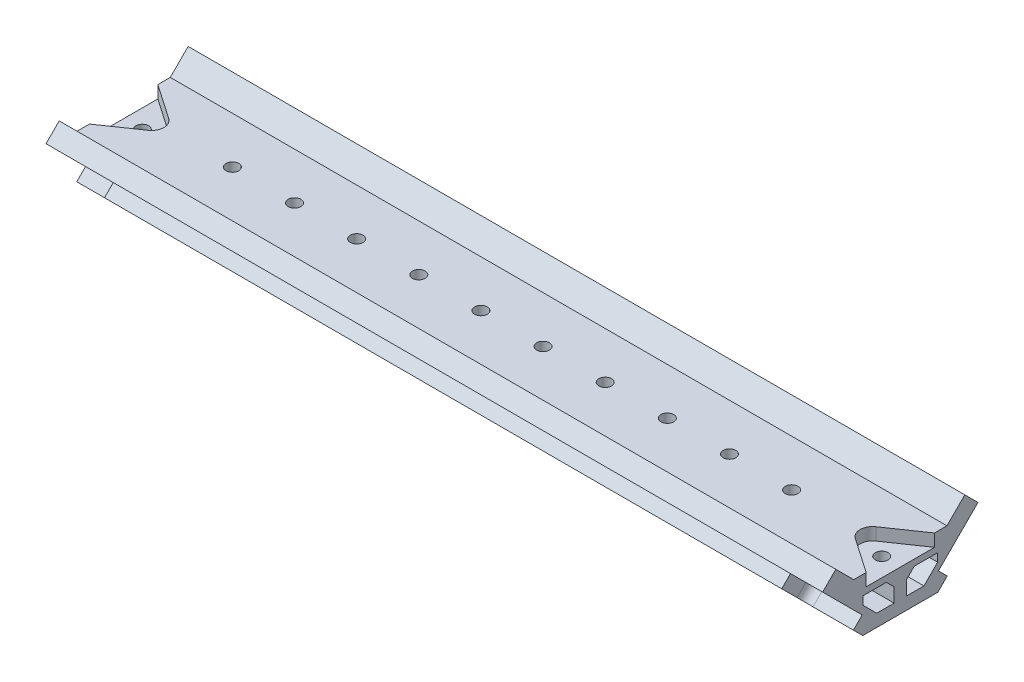
SolidWorks part; units mm, degrees
ref_plane "Front Plane" through (0, 0, 0) normal (0, 0, 1) x (1, 0, 0)
ref_plane "Top Plane" through (0, 0, 0) normal (0, 1, 0) x (1, 0, 0)
ref_plane "Right Plane" through (0, 0, 0) normal (1, 0, 0) x (0, 0, -1)
sketch "Sketch1" plane through (0, 0, 0) normal (1, 0, 0) x (0, 0, -1)
  line L1 (-25, 0) -> (25, 0)
  line L2 (-25, 0) -> (-25, 30)
  line L3 (-25, 30) -> (25, 30)
  line L4 (25, 0) -> (25, 30)
  dimension "D1" = 30
  dimension "D2" = 50
  dimension "D3" = 25
extrude "Boss-Extrude1" add sketch "Sketch1" along normal blind 125 and the other way blind 125
sketch "Sketch2" plane through (125, 0, 0) normal (1, 0, 0) x (0, 0, -1)
  line L0 (-10, 0) -> (-25, 15)
  line L1 (-25, 0) -> (25, 0) construction
  line L2 (-25, 30) -> (-25, 0) construction
  line L3 (-25, 15) -> (-25, 0)
  line L4 (-25, 0) -> (-10, 0)
  line L5 (25, 15) -> (10, 0)
  line L6 (25, 0) -> (25, 30) construction
  line L7 (10, 0) -> (25, 0)
  line L8 (25, 0) -> (25, 15)
  dimension "D1" = 15
  dimension "D2" = 15
  dimension "D3" = 15
  dimension "D4" = 15
extrude "Cut-Extrude1" cut sketch "Sketch2" against normal through all
sketch "Sketch4" plane through (125, 0, 0) normal (1, 0, 0) x (0, 0, -1)
  line L8 (-22.1716, 12.1716) -> (-19.3431, 15)
  line L9 (-10, 0) -> (-25, 15) construction
  line L10 (-19.3431, 15) -> (-25, 20.6569)
  line L11 (-25, 30) -> (-25, 15) construction
  line L12 (-25, 20.6569) -> (-25, 15)
  line L13 (-25, 15) -> (-22.1716, 12.1716)
  line L14 (22.1716, 12.1716) -> (19.3431, 15)
  line L15 (25, 15) -> (10, 0) construction
  line L16 (19.3431, 15) -> (25, 20.6569)
  line L17 (25, 15) -> (25, 30) construction
  line L18 (25, 20.6569) -> (25, 15)
  line L19 (25, 15) -> (22.1716, 12.1716)
  dimension "D1" = 4
  dimension "D2" = 4
  dimension "D3" = 8
  dimension "D4" = 8
extrude "Cut-Extrude2" cut sketch "Sketch4" against normal through all
sketch "Sketch5" plane through (125, 0, 0) normal (1, 0, 0) x (0, 0, -1)
  line L0 (-25, 20.6569) -> (-20.7574, 24.8995)
  line L1 (-20.7574, 24.8995) -> (-15, 19.1421)
  line L2 (-15, 19.1421) -> (15, 19.1421)
  line L3 (15, 19.1421) -> (20.7574, 24.8995)
  line L4 (20.7574, 24.8995) -> (25, 20.6569)
  line L5 (25, 20.6569) -> (25, 30)
  line L6 (25, 30) -> (-25, 30)
  line L7 (-25, 30) -> (-25, 20.6569)
  line L8 (25, 20.6569) -> (19.3431, 15) construction
  point P6 (20.5583, 24.6906)
  point P18 (-20.7574, 24.8995)
  dimension "D1" = 6
  dimension "D2" = 6
  dimension "D3" = 30
  dimension "D4" = 15
extrude "Cut-Extrude3" cut sketch "Sketch5" against normal through all
sketch "Sketch6" plane through (0, 19.1421, 0) normal (0, 1, 0) x (1, 0, 0)
  circle A0 centre (-10, 0) radius 2.05
  circle A1 centre (10, 0) radius 2.05
  circle A2 centre (30, 0) radius 2.05
  circle A3 centre (50, 0) radius 2.05
  circle A4 centre (70, 0) radius 2.05
  circle A5 centre (90, 0) radius 2.05
  circle A6 centre (-30, 0) radius 2.05
  circle A7 centre (-50, 0) radius 2.05
  circle A8 centre (-70, 0) radius 2.05
  circle A9 centre (-90, 0) radius 2.05
  dimension "D1" = 4.1
  dimension "D2" = 20
  dimension "D3" = 10
  dimension "D4" = 20
  dimension "D5" = 20
  dimension "D6" = 20
  dimension "D7" = 20
  dimension "D8" = 20
  dimension "D9" = 20
  dimension "D10" = 20
  dimension "D11" = 20
extrude "Cut-Extrude4" cut sketch "Sketch6" against normal blind 6
sketch "Sketch7" plane through (-125, 0, 0) normal (-1, 0, 0) x (0, 0, 1)
  line L0 (-8.3431, 4) -> (-2, 4)
  line L1 (8.3431, 4) -> (14.9902, 10.647)
  line L3 (10.4951, 15.1421) -> (6.4951, 15.1421)
  line L5 (-14.9902, 10.647) -> (-8.3431, 4)
  line L6 (10, 0) -> (22.1716, 12.1716) construction
  line L7 (-22.1716, 12.1716) -> (-10, 0) construction
  line L8 (10, 0) -> (-10, 0) construction
  line L9 (-2, 10.647) -> (-2, 4)
  line L10 (2, 10.647) -> (2, 4)
  line L11 (-6.4951, 15.1421) -> (-10.4951, 15.1421)
  line L12 (2, 4) -> (8.3431, 4)
  line L13 (-6.4951, 15.1421) -> (-2, 10.647)
  line L14 (-14.9902, 10.647) -> (-10.4951, 15.1421)
  line L15 (14.9902, 10.647) -> (10.4951, 15.1421)
  line L16 (6.4951, 15.1421) -> (2, 10.647)
  line L17 (15, 19.1421) -> (-15, 19.1421) construction
  point P2 (0, 0)
  point P4 (0, 0)
  point P12 (14.8624, 10.5192)
  point P13 (-6.2846, 15.1421)
  point P25 (14.3409, 9.9978)
  dimension "D1" = 2
  dimension "D2" = 4
  dimension "D3" = 4
  dimension "D4" = 4
  dimension "D5" = 90
  dimension "D6" = 90
  dimension "D7" = 2
  dimension "D8" = 135
  dimension "D9" = 4
  dimension "D10" = 4
extrude "Cut-Extrude5" cut sketch "Sketch7" against normal through all
sketch "Sketch8" plane through (-125, 0, 0) normal (-1, 0, 0) x (0, 0, 1)
  line L0 (-12, 13.6372) -> (-12, 7.6569)
  line L1 (-10.4951, 15.1421) -> (-14.9902, 10.647) construction
  line L2 (-14.9902, 10.647) -> (-8.3431, 4) construction
  line L3 (-12, 7.6569) -> (-14.9902, 10.647)
  line L4 (-14.9902, 10.647) -> (-12, 13.6372)
  line L5 (12, 13.6372) -> (12, 7.6569)
  line L6 (14.9902, 10.647) -> (10.4951, 15.1421) construction
  line L7 (8.3431, 4) -> (14.9902, 10.647) construction
  line L8 (12, 7.6569) -> (14.9902, 10.647)
  line L9 (14.9902, 10.647) -> (12, 13.6372)
  point P6 (0, 0)
  dimension "D1" = 12
extrude "Boss-Extrude2" add sketch "Sketch8" against normal through all
sketch "Sketch9" plane through (125, 0, 0) normal (1, 0, 0) x (0, 0, -1)
  line L0 (-16.0858, 6.0858) -> (16.0858, 6.0858)
  line L1 (-10, 0) -> (-22.1716, 12.1716) construction
  line L2 (22.1716, 12.1716) -> (10, 0) construction
  line L3 (16.0858, 6.0858) -> (10, 0)
  line L4 (10, 0) -> (-10, 0)
  line L5 (-10, 0) -> (-16.0858, 6.0858)
extrude "Boss-Extrude3" add sketch "Sketch9" against normal through all
sketch "Sketch10" plane through (125, 0, 0) normal (1, 0, 0) x (0, 0, -1)
  line L0 (-12.0858, 2.0858) -> (12.0858, 2.0858)
  line L1 (-10, 0) -> (-22.1716, 12.1716) construction
  line L2 (22.1716, 12.1716) -> (10, 0) construction
  line L3 (12.0858, 2.0858) -> (10, 0)
  line L4 (10, 0) -> (-10, 0)
  line L5 (-10, 0) -> (-12.0858, 2.0858)
  line L6 (-2, 6.0858) -> (-10.4289, 6.0858) construction
  dimension "D1" = 4
extrude "Cut-Extrude6" cut sketch "Sketch10" against normal through all
sketch "Sketch11" plane through (0, -5, 5) normal (0, -0.7071, 0.7071) x (1, 0, 0)
  line L0 (125, 14.2843) -> (109, 14.2843)
  line L1 (125, 10.0208) -> (125, 24.2843) construction
  line L2 (109, 14.2843) -> (109, 24.2843)
  line L3 (-125, 24.2843) -> (125, 24.2843) construction
  line L4 (109, 24.2843) -> (125, 24.2843)
  line L5 (125, 24.2843) -> (125, 14.2843)
  line L6 (-125, 10.0208) -> (-125, 24.2843) construction
  line L7 (-125, 14.2843) -> (-109, 14.2843)
  line L8 (-125, 14.2843) -> (-125, 24.2843)
  line L9 (-125, 24.2843) -> (-109, 24.2843)
  line L10 (-109, 14.2843) -> (-109, 24.2843)
  line L11 (-125, 24.2843) -> (125, 24.2843) construction
  point P17 (0, 0)
  dimension "D1" = 10
  dimension "D2" = 16
  dimension "D3" = 16
extrude "Cut-Extrude7" cut sketch "Sketch11" against normal up to surface (4 mm away) up to face at (0, 17.8284, 22.1716)
sketch "Sketch12" plane through (0, -5, -5) normal (0, -0.7071, -0.7071) x (-1, 0, 0)
  line L13 (125, 32.2843) -> (-125, 32.2843) construction
  line L18 (-125, 14.2843) -> (-109, 14.2843)
  line L19 (-125, 14.2843) -> (-125, 32.2843)
  line L20 (-125, 32.2843) -> (-109, 32.2843)
  line L21 (-109, 14.2843) -> (-109, 32.2843)
  line L23 (125, 14.2843) -> (109, 14.2843)
  line L24 (125, 14.2843) -> (125, 32.2843)
  line L25 (125, 32.2843) -> (109, 32.2843)
  line L26 (109, 14.2843) -> (109, 32.2843)
  point P15 (0, 0)
  point P18 (-106.5228, 15.2998)
  point P19 (-125, 15.2998)
  point P20 (0, 0)
  point P21 (125, 32.2843)
  point P23 (-125, 32.2843)
  dimension "D1" = 10
  dimension "D2" = 16
  dimension "D3" = 16
extrude "Cut-Extrude11" cut sketch "Sketch12" against normal up to surface (4 mm away) up to face at (0, 17.8284, -22.1716)
sketch "Sketch13" plane through (125, 0, 0) normal (1, 0, 0) x (0, 0, -1)
  line L0 (7.6005, 6.0858) -> (13.5147, 12)
  line L1 (10.4289, 6.0858) -> (2, 6.0858) construction
  line L2 (13.5147, 12) -> (14.9289, 10.5858)
  line L3 (12.2721, 7.9289) -> (19.3431, 15) construction
  line L4 (14.9289, 10.5858) -> (10.4289, 6.0858)
  line L5 (10.4289, 6.0858) -> (7.6005, 6.0858)
  line L6 (-7.6005, 6.0858) -> (-13.5147, 12)
  line L7 (-2, 6.0858) -> (-10.4289, 6.0858) construction
  line L8 (-13.5147, 12) -> (-14.9289, 10.5858)
  line L9 (-19.3431, 15) -> (-12.2721, 7.9289) construction
  line L10 (-14.9289, 10.5858) -> (-10.4289, 6.0858)
  line L11 (-10.4289, 6.0858) -> (-7.6005, 6.0858)
  point P13 (0, 0)
  dimension "D1" = 2
  dimension "D2" = 2
  dimension "D3" = 12
extrude "Boss-Extrude4" add sketch "Sketch13" against normal through all
sketch "Sketch14" plane through (0, 19.1421, 0) normal (0, 1, 0) x (1, 0, 0)
  line L13 (125, 11) -> (109, 0)
  line L14 (125, -15) -> (125, 15) construction
  line L15 (109, 0) -> (125, -11)
  line L16 (125, -11) -> (125, 11)
  line L17 (-125, 11) -> (-109, 0)
  line L18 (-125, -15) -> (-125, 15) construction
  line L19 (-109, 0) -> (-125, -11)
  line L20 (-125, -11) -> (-125, 11)
  point P10 (-125, -8.6578)
  point P13 (0, 0)
  point P16 (0, 0)
  dimension "D1" = 4
  dimension "D2" = 4
  dimension "D3" = 16
extrude "Cut-Extrude12" cut sketch "Sketch14" against normal blind 4
sketch "Sketch15" plane through (-125, 0, 0) normal (-1, 0, 0) x (0, 0, 1)
  line L1 (-15, 15.1421) -> (15, 15.1421)
  line L2 (-15, 15.1421) -> (-15, 13.1421)
  line L3 (-15, 13.1421) -> (15, 13.1421)
  line L4 (15, 15.1421) -> (15, 13.1421)
  point P5 (0, 0)
  point P6 (-13.7129, 15.1683)
  dimension "D1" = 2
  dimension "D2" = 4
  dimension "D3" = 30
  dimension "D4" = 15
extrude "Boss-Extrude5" add sketch "Sketch15" against normal through all
fillet "Fillet1" radius 4 2 edges at (109, 17.1421, 0) (-109, 17.1421, 0)
fillet "Fillet2" radius 3 4 edges at (109, 6.5147, -13.6863) (-109, 6.5147, -13.6863) (-109, 6.5147, 13.6863) (109, 6.5147, 13.6863)
sketch "Sketch16" plane through (0, 15.1421, 0) normal (0, 1, 0) x (1, 0, 0)
  circle A0 centre (119, 0) radius 2.05
  circle A1 centre (-119, 0) radius 2.05
  point P4 (0, 0)
  dimension "D1" = 4.1
  dimension "D2" = 6
  dimension "D3" = 6
extrude "Cut-Extrude13" cut sketch "Sketch16" against normal blind 6
sketch "Sketch17" plane through (0, -2.1716, -2.1716) normal (0, -0.7071, -0.7071) x (-1, 0, 0)
  circle A0 centre (-115, 19.2843) radius 2.05
  circle A1 centre (115, 19.2843) radius 2.05
  point P4 (0, 0)
  dimension "D1" = 4.1
  dimension "D2" = 5
  dimension "D3" = 10
  dimension "D4" = 10
extrude "Cut-Extrude14" cut sketch "Sketch17" against normal blind 6
sketch "Sketch18" plane through (0, -2.1716, 2.1716) normal (0, -0.7071, 0.7071) x (1, 0, 0)
  circle A0 centre (-115, 19.2843) radius 2.05
  circle A1 centre (115, 19.2843) radius 2.05
  point P4 (0, 0)
  dimension "D1" = 4.1
  dimension "D2" = 10
  dimension "D3" = 10
  dimension "D4" = 5
extrude "Cut-Extrude15" cut sketch "Sketch18" against normal blind 6
